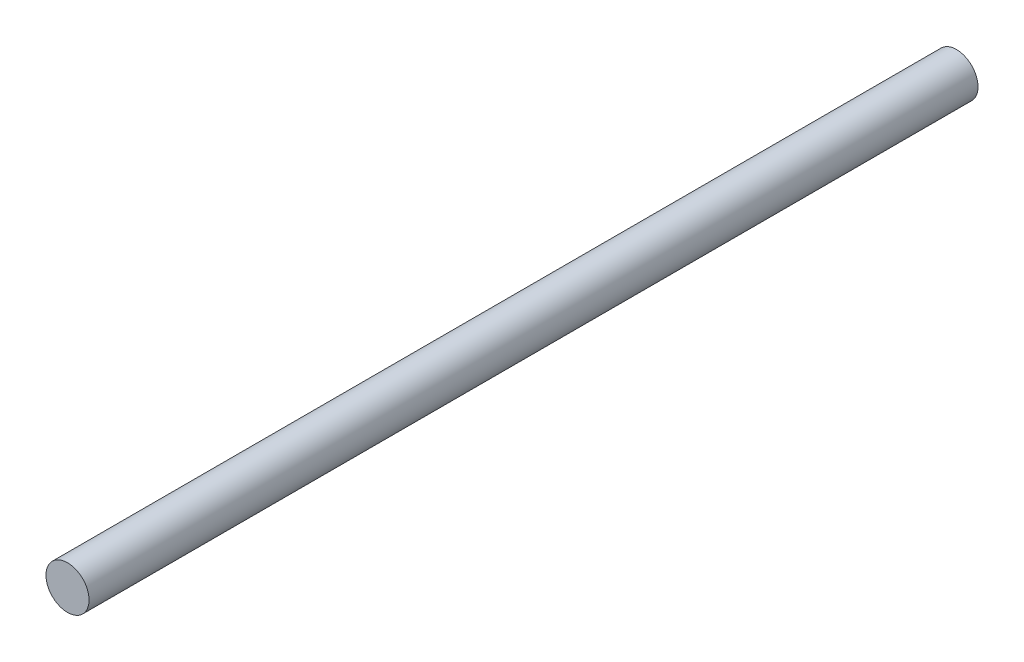
SolidWorks part; units mm, degrees
ref_plane "Front Plane" through (0, 0, 0) normal (0, 0, 1) x (1, 0, 0)
ref_plane "Top Plane" through (0, 0, 0) normal (0, 1, 0) x (1, 0, 0)
ref_plane "Right Plane" through (0, 0, 0) normal (1, 0, 0) x (0, 0, -1)
sketch "Sketch1" plane through (0, 0, 0) normal (0, 0, 1) x (1, 0, 0)
  circle A0 centre (0, 0) radius 4
  dimension "D1" = 8
extrude "Boss-Extrude1" add sketch "Sketch1" along normal blind 165
